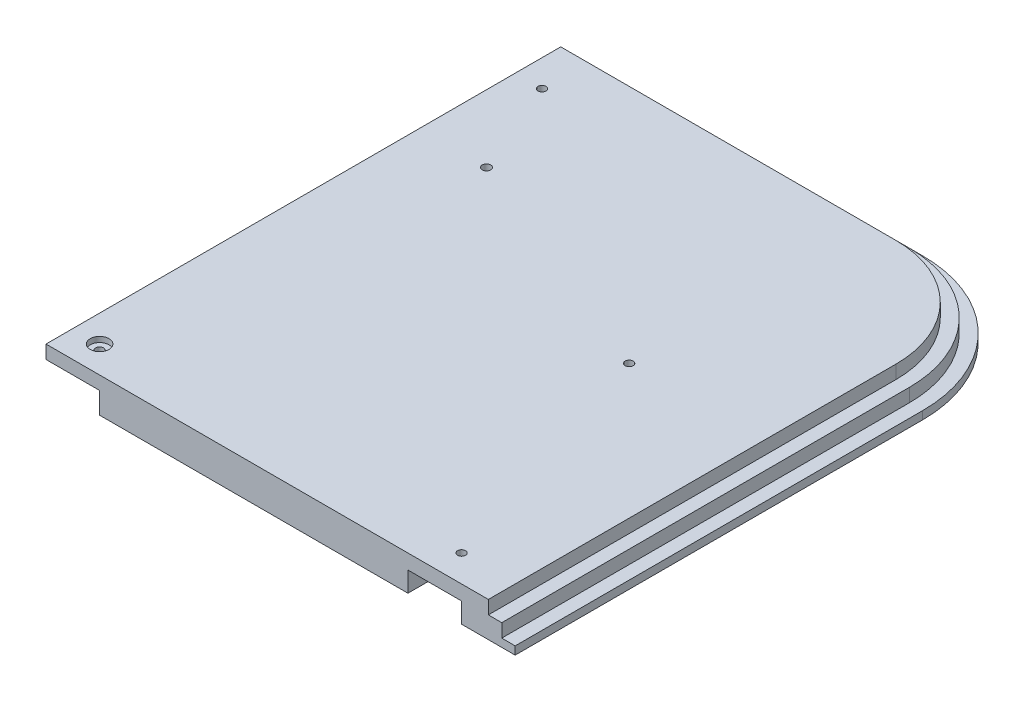
SolidWorks part; units mm, degrees
material "PETG"
ref_plane "Alzado" through (0, 0, 0) normal (0, 0, 1) x (1, 0, 0)
ref_plane "Planta" through (0, 0, 0) normal (0, 1, 0) x (1, 0, 0)
ref_plane "Vista lateral" through (0, 0, 0) normal (1, 0, 0) x (0, 0, -1)
sketch "Croquis1" plane through (0, 0, 0) normal (0, 1, 0) x (1, 0, 0)
  line L1 (125, 225) -> (-125, 225)
  line L2 (175, 175) -> (175, -175)
  line L3 (125, -225) -> (-125, -225)
  line L4 (-175, 175) -> (-175, -175)
  line L5 (175, 225) -> (-175, -225) construction
  line L6 (175, -225) -> (-175, 225) construction
  arc A0 (-125, -225) -> (-175, -175) centre (-125, -175) cw
  arc A1 (175, -175) -> (125, -225) centre (125, -175) cw
  arc A2 (125, 225) -> (175, 175) centre (125, 175) cw
  arc A3 (-125, 225) -> (-175, 175) centre (-125, 175) ccw
  point P0 (0, 0)
  dimension "D3" = 50
  dimension "D1" = 450
  dimension "D2" = 350
extrude "Saliente-Extruir1" add sketch "Croquis1" along normal blind 3
sketch "Croquis2" plane through (0, 3, 0) normal (0, 1, 0) x (1, 0, 0)
  line L8 (-125, -220) -> (125, -220)
  line L9 (170, -175) -> (170, 175)
  line L10 (125, 220) -> (-125, 220)
  line L11 (-170, 175) -> (-170, -175)
  line L12 (-125, -220) -> (125, -220)
  line L13 (170, -175) -> (170, 175)
  line L14 (125, 220) -> (-125, 220)
  line L15 (-170, 175) -> (-170, -175)
  arc A8 (-170, -175) -> (-125, -220) centre (-125, -175) ccw
  arc A9 (125, -220) -> (170, -175) centre (125, -175) ccw
  arc A10 (170, 175) -> (125, 220) centre (125, 175) ccw
  arc A11 (-125, 220) -> (-170, 175) centre (-125, 175) ccw
  arc A12 (-170, -175) -> (-125, -220) centre (-125, -175) ccw
  arc A13 (125, -220) -> (170, -175) centre (125, -175) ccw
  arc A14 (170, 175) -> (125, 220) centre (125, 175) ccw
  arc A15 (-125, 220) -> (-170, 175) centre (-125, 175) ccw
  dimension "D1" = 5
extrude "Saliente-Extruir2" add sketch "Croquis2" along normal blind 5
sketch "Croquis3" plane through (0, 8, 0) normal (0, 1, 0) x (1, 0, 0)
  line L8 (-125, -215) -> (125, -215)
  line L9 (165, -175) -> (165, 175)
  line L10 (125, 215) -> (-125, 215)
  line L11 (-165, 175) -> (-165, -175)
  line L12 (-125, -215) -> (125, -215)
  line L13 (165, -175) -> (165, 175)
  line L14 (125, 215) -> (-125, 215)
  line L15 (-165, 175) -> (-165, -175)
  arc A8 (-165, -175) -> (-125, -215) centre (-125, -175) ccw
  arc A9 (125, -215) -> (165, -175) centre (125, -175) ccw
  arc A10 (165, 175) -> (125, 215) centre (125, 175) ccw
  arc A11 (-125, 215) -> (-165, 175) centre (-125, 175) ccw
  arc A12 (-165, -175) -> (-125, -215) centre (-125, -175) ccw
  arc A13 (125, -215) -> (165, -175) centre (125, -175) ccw
  arc A14 (165, 175) -> (125, 215) centre (125, 175) ccw
  arc A15 (-125, 215) -> (-165, 175) centre (-125, 175) ccw
  dimension "D1" = 5
extrude "Saliente-Extruir3" add sketch "Croquis3" along normal blind 5
sketch "Croquis6" plane through (0, 13, 0) normal (0, 1, 0) x (1, 0, 0)
  line L0 (0, 0) -> (0, -215) construction
  line L1 (-125, -215) -> (125, -215) construction
  circle A0 centre (-87, -130) radius 2.25
  circle A1 centre (-87, -70) radius 2.25
  circle A2 centre (-87, -10) radius 2.25
  circle A3 centre (87, -130) radius 2.25
  circle A4 centre (87, -70) radius 2.25
  circle A5 centre (87, -10) radius 2.25
  dimension "D1" = 4.5
  dimension "D2" = 4.5
  dimension "D3" = 4.5
  dimension "D4" = 87
  dimension "D5" = 60
  dimension "D6" = 60
  dimension "D7" = 10
extrude "Cortar-Extruir3" cut sketch "Croquis6" against normal blind 5
sketch "Croquis7" plane through (0, 13, 0) normal (0, 1, 0) x (1, 0, 0)
  line L0 (0, -11.4875) -> (0, -220) construction
  line L1 (-125, -220) -> (125, -220) construction
  circle A0 centre (-115, -70) radius 1.5
  circle A1 centre (-115, 125.5) radius 1.5
  circle A2 centre (115, -70) radius 1.5
  circle A3 centre (115, 125.5) radius 1.5
  dimension "D1" = 3
  dimension "D2" = 3
  dimension "D3" = 115
  dimension "D4" = 70
  dimension "D5" = 125.5
  dimension "D6" = 115
extrude "Cortar-Extruir4" cut sketch "Croquis7" against normal through all
sketch "Croquis8" plane through (0, 13, 0) normal (0, 1, 0) x (1, 0, 0)
  line L0 (13.0147, -158) -> (13.0147, -178) construction
  line L4 (16.0147, -158) -> (16.0147, -178)
  line L5 (10.0147, -158) -> (10.0147, -178)
  line L6 (25.0147, -158) -> (25.0147, -178) construction
  line L7 (28.0147, -158) -> (28.0147, -178)
  line L8 (22.0147, -158) -> (22.0147, -178)
  line L9 (25.0147, -106) -> (25.0147, -126) construction
  line L10 (28.0147, -106) -> (28.0147, -126)
  line L11 (22.0147, -106) -> (22.0147, -126)
  line L12 (13.0147, -106) -> (13.0147, -126) construction
  line L15 (16.0147, -106) -> (16.0147, -126)
  line L16 (10.0147, -106) -> (10.0147, -126)
  arc A0 (10.0147, -168) -> (13.0147, -171) centre (13.0147, -168) ccw construction
  arc A1 (25.0147, -171) -> (28.0147, -168) centre (25.0147, -168) ccw construction
  arc A2 (16.0147, -116) -> (13.0147, -113) centre (13.0147, -116) ccw construction
  arc A3 (22.0147, -116) -> (25.0147, -119) centre (25.0147, -116) ccw construction
  arc A6 (16.0147, -158) -> (10.0147, -158) centre (13.0147, -158) ccw
  arc A7 (10.0147, -178) -> (16.0147, -178) centre (13.0147, -178) ccw
  arc A8 (28.0147, -158) -> (22.0147, -158) centre (25.0147, -158) ccw
  arc A9 (22.0147, -178) -> (28.0147, -178) centre (25.0147, -178) ccw
  arc A10 (28.0147, -106) -> (22.0147, -106) centre (25.0147, -106) ccw
  arc A11 (22.0147, -126) -> (28.0147, -126) centre (25.0147, -126) ccw
  arc A14 (16.0147, -106) -> (10.0147, -106) centre (13.0147, -106) ccw
  arc A15 (10.0147, -126) -> (16.0147, -126) centre (13.0147, -126) ccw
  arc A16 (13.0147, -113) -> (10.0147, -116) centre (13.0147, -116) ccw construction
  arc A17 (10.0147, -116) -> (13.0147, -119) centre (13.0147, -116) ccw construction
  arc A18 (13.0147, -119) -> (16.0147, -116) centre (13.0147, -116) ccw construction
  arc A19 (28.0147, -116) -> (25.0147, -113) centre (25.0147, -116) ccw construction
  arc A20 (25.0147, -119) -> (28.0147, -116) centre (25.0147, -116) ccw construction
  arc A21 (25.0147, -113) -> (22.0147, -116) centre (25.0147, -116) ccw construction
  arc A22 (25.0147, -165) -> (22.0147, -168) centre (25.0147, -168) ccw construction
  arc A23 (22.0147, -168) -> (25.0147, -171) centre (25.0147, -168) ccw construction
  arc A24 (28.0147, -168) -> (25.0147, -165) centre (25.0147, -168) ccw construction
  arc A25 (16.0147, -168) -> (13.0147, -165) centre (13.0147, -168) ccw construction
  arc A26 (13.0147, -171) -> (16.0147, -168) centre (13.0147, -168) ccw construction
  arc A27 (13.0147, -165) -> (10.0147, -168) centre (13.0147, -168) ccw construction
  point P10 (13.0147, -168)
  point P16 (25.0147, -168)
  point P23 (25.0147, -116)
  point P32 (13.0147, -116)
  dimension "D1" = 6
  dimension "D2" = 6
  dimension "D3" = 6
  dimension "D4" = 6
  dimension "D5" = 12
  dimension "D6" = 52
  dimension "D7" = 116
  dimension "D8" = 13.0147
  dimension "D9" = 20
  dimension "D10" = 20
  dimension "D11" = 20
  dimension "D12" = 20
extrude "Cortar-Extruir5" cut sketch "Croquis8" against normal blind 8
sketch "Croquis9" plane through (0, 13, 0) normal (0, 1, 0) x (1, 0, 0)
  circle A0 centre (13.0147, -168) radius 1.5
  circle A1 centre (25.0147, -168) radius 1.5
  circle A2 centre (13.0147, -116) radius 1.5
  circle A3 centre (25.0147, -116) radius 1.5
  circle A4 centre (-87, -70) radius 2.25 construction
  circle A5 centre (-87, -130) radius 1.5
  circle A6 centre (-87, -70) radius 1.5
  circle A7 centre (-87, -10) radius 1.5
  circle A8 centre (87, -10) radius 1.5
  circle A9 centre (87, -70) radius 1.5
  circle A10 centre (87, -130) radius 1.5
  dimension "D1" = 3
  dimension "D2" = 3
  dimension "D3" = 3
  dimension "D4" = 3
  dimension "D5" = 100.0147
  dimension "D6" = 112.0147
  dimension "D7" = 46
  dimension "D8" = 98
extrude "Cortar-Extruir6" cut sketch "Croquis9" against normal through all
sketch "Croquis10" plane through (0, 13, 0) normal (0, 1, 0) x (1, 0, 0)
  line L1 (50, -120) -> (75, -120)
  line L2 (50, -120) -> (50, -170)
  line L3 (50, -170) -> (75, -170)
  line L4 (75, -120) -> (75, -170)
  dimension "D1" = 50
  dimension "D2" = 25
  dimension "D3" = 120
  dimension "D4" = 50
extrude "Cortar-Extruir7" cut sketch "Croquis10" against normal blind 5
chamfer "Chaflán1" distance 5 angle 45 4 edges at (62.5, 13, 120) (50, 13, 145) (62.5, 13, 170) (75, 13, 145)
sketch "Croquis13" plane through (0, 13, 0) normal (0, 1, 0) x (1, 0, 0)
  circle A0 centre (-60, -50) radius 2.25
  circle A1 centre (-20, -50) radius 2.25
  circle A2 centre (-20, -90) radius 2.25
  circle A3 centre (-60, -90) radius 2.25
  circle A4 centre (-20, -50) radius 3.5
  circle A5 centre (-60, -50) radius 3.5
  circle A6 centre (-60, -90) radius 3.5
  circle A7 centre (-20, -90) radius 3.5
  dimension "D1" = 4.5
  dimension "D2" = 40
  dimension "D6" = 7
  dimension "D3" = 40
  dimension "D4" = 20
  dimension "D5" = 50
extrude "Saliente-Extruir4" add sketch "Croquis13" along normal blind 25
sketch "Croquis14" plane through (0, 13, 0) normal (0, 1, 0) x (1, 0, 0)
  circle A0 centre (3.15, -40) radius 1.25
  circle A1 centre (67.55, -40) radius 1.25
  circle A3 centre (67.55, -40) radius 3
  circle A4 centre (3.15, -40) radius 3
  circle A5 centre (3, -91.9) radius 3
  circle A6 centre (3, -91.9) radius 1.25
  circle A7 centre (67.4, -91.9) radius 3
  circle A8 centre (67.4, -91.9) radius 1.25
  circle A9 centre (-10, -102.9) radius 1.5
  circle A10 centre (-10, -102.9) radius 3
  circle A11 centre (-10, -118.1085) radius 3
  circle A12 centre (-10, -118.1085) radius 1.5
  dimension "D1" = 2.5
  dimension "D2" = 6
  dimension "D7" = 3
  dimension "D8" = 6
  dimension "D9" = 6
  dimension "D10" = 3
  dimension "D3" = 51.9
  dimension "D4" = 64.4
  dimension "D5" = 40
  dimension "D6" = 3
  dimension "D11" = 11
  dimension "D12" = 13
  dimension "D13" = 15.2085
  dimension "D14" = 64.4
  dimension "D15" = 0.15
extrude "Saliente-Extruir5" add sketch "Croquis14" along normal blind 10
sketch "Croquis12" plane through (0, 13, 0) normal (0, 1, 0) x (1, 0, 0)
  line L0 (-25.1, 12) -> (-25.1, 13.6) construction
  line L1 (-25.1, 12) -> (-23.5, 12) construction
  line L2 (25.1, 12) -> (23.5, 12) construction
  line L3 (25.1, 12) -> (25.1, 13.6) construction
  line L4 (25.1, 162.2) -> (25.1, 160.6) construction
  line L5 (25.1, 162.2) -> (23.5, 162.2) construction
  line L6 (-25.1, 162.2) -> (-23.5, 162.2) construction
  line L7 (-25.1, 162.2) -> (-25.1, 160.6) construction
  circle A0 centre (-25.1, 162.2) radius 1.6
  circle A1 centre (25.1, 162.2) radius 1.6
  circle A2 centre (-25.1, 12) radius 1.6
  circle A3 centre (25.1, 12) radius 1.6
  dimension "D4" = 3.2
  dimension "D1" = 12
  dimension "D2" = 47
  dimension "D3" = 23.5
  dimension "D5" = 147
  dimension "D6" = 147
extrude "Cortar-Extruir9" cut sketch "Croquis12" against normal through all
sketch "Croquis11" plane through (0, 0, 0) normal (0, -1, 0) x (1, 0, 0)
  line L0 (13.0147, 168) -> (25.0147, 168) construction
  line L1 (13.0147, 188) -> (25.0147, 188)
  line L2 (13.0147, 148) -> (25.0147, 148)
  line L3 (13.0147, 116) -> (25.0147, 116) construction
  line L4 (13.0147, 136) -> (25.0147, 136)
  line L5 (13.0147, 96) -> (25.0147, 96)
  circle A4 centre (87, 130) radius 6
  circle A5 centre (87, 70) radius 6
  circle A6 centre (87, 10) radius 6
  circle A7 centre (-87, 10) radius 6
  circle A8 centre (-87, 70) radius 6
  circle A9 centre (-87, 130) radius 6
  circle A10 centre (-115, 70) radius 6
  circle A11 centre (115, 70) radius 6
  circle A12 centre (115, -125.5) radius 6
  circle A15 centre (-115, -125.5) radius 6
  arc A16 (13.0147, 188) -> (13.0147, 148) centre (13.0147, 168) ccw
  arc A17 (25.0147, 148) -> (25.0147, 188) centre (25.0147, 168) ccw
  circle A18 centre (-25.1, -162.2) radius 6
  arc A19 (13.0147, 136) -> (13.0147, 96) centre (13.0147, 116) ccw
  arc A20 (25.0147, 96) -> (25.0147, 136) centre (25.0147, 116) ccw
  circle A21 centre (25.1, -162.2) radius 6
  circle A22 centre (-25.1, -12) radius 6
  circle A23 centre (25.1, -12) radius 6
  point P3 (19.0147, 168)
  point P10 (19.0147, 116)
  dimension "D1" = 12
  dimension "D2" = 20
  dimension "D3" = 20
extrude "Cortar-Extruir8" cut sketch "Croquis11" against normal blind 5
sketch "Croquis16" plane through (0, 0, 0) normal (1, 0, 0) x (0, 0, -1)
  line L0 (-175, 0) -> (175, 0) construction
  line L5 (-175, 8) -> (175, 8) construction
  line L6 (2, 8) -> (42, 8)
  line L7 (2, 8) -> (2, 0)
  line L8 (2, 0) -> (42, 0)
  line L9 (42, 8) -> (42, 0)
  dimension "D1" = 40
  dimension "D2" = 2
extrude "Cortar-Extruir10" cut sketch "Croquis16" against normal mid plane 40
sketch "Croquis17" plane through (0, 13, 0) normal (0, 1, 0) x (1, 0, 0)
  line L0 (-175, 23) -> (0, 23) construction
  line L2 (0, 23) -> (0, -225) construction
  line L3 (-125, -225) -> (125, -225) construction
  line L4 (-175, 175) -> (-175, -175) construction
  line L5 (-175, 23) -> (-175, 225)
  line L6 (-175, 225) -> (0, 225)
  line L7 (175, 225) -> (175, 23) construction
  line L8 (175, -225) -> (0, -225)
  line L9 (125, 225) -> (-125, 225) construction
  line L10 (175, -175) -> (175, 175) construction
  line L11 (0, 23) -> (175, 23)
  line L12 (-175, 23) -> (-175, -225)
  line L13 (-175, -225) -> (0, -225)
  line L14 (175, 23) -> (175, -225)
  line L15 (0, 23) -> (0, 225)
  line L16 (0, 225) -> (175, 225) construction
  dimension "D1" = 248
extrude "Cortar-Extruir11" cut sketch "Croquis17" against normal mid plane 60
sketch "Croquis19" plane through (0, 13, 0) normal (0, 1, 0) x (1, 0, 0)
  line L0 (175, 23) -> (175, 175) construction
  line L1 (165, 23) -> (0, 23) construction
  line L2 (0, 23) -> (0, 215) construction
  line L3 (125, 225) -> (0, 225) construction
  circle A0 centre (10, 33) radius 1.5
  circle A1 centre (10, 198) radius 1.5
  circle A2 centre (145, 33) radius 1.5
  dimension "D1" = 3
  dimension "D2" = 3
  dimension "D3" = 3
  dimension "D4" = 30
  dimension "D5" = 10
  dimension "D6" = 10
  dimension "D7" = 27
  dimension "D8" = 10
extrude "Cortar-Extruir12" cut sketch "Croquis19" against normal blind 70
sketch "Croquis20" plane through (0, 0, 0) normal (-1, 0, 0) x (0, 0, 1)
  line L0 (-225, 0) -> (-225, 3) construction
  line L6 (-208, 7.5) -> (-188, 7.5)
  line L7 (-208, 7.5) -> (-208, 0)
  line L8 (-208, 0) -> (-188, 0)
  line L9 (-188, 7.5) -> (-188, 0)
  line L11 (-225, 0) -> (-42, 0) construction
  dimension "D1" = 17
  dimension "D2" = 20
  dimension "D3" = 7.5
extrude "Cortar-Extruir13" cut sketch "Croquis20" against normal blind 20
sketch "Croquis21" plane through (0, 0, -23) normal (0, 0, 1) x (1, 0, 0)
  line L0 (175, 0) -> (20, 0) construction
  line L1 (135, 7.5) -> (155, 7.5)
  line L2 (135, 7.5) -> (135, 0)
  line L3 (135, 0) -> (155, 0)
  line L4 (155, 7.5) -> (155, 0)
  line L5 (175, 0) -> (175, 3) construction
  dimension "D1" = 7.5
  dimension "D2" = 20
  dimension "D3" = 20
extrude "Cortar-Extruir14" cut sketch "Croquis21" against normal blind 20
sketch "Croquis22" plane through (0, 0, 0) normal (0, -1, 0) x (1, 0, 0)
  line L5 (27, -208) -> (27, -181)
  line L6 (27, -181) -> (0, -181)
  line L7 (27, -215) -> (27, -181)
  line L8 (27, -181) -> (7, -181)
  line L28 (128, -50) -> (128, -30)
  line L29 (128, -30) -> (27, -30)
  line L30 (27, -30) -> (27, -49)
  line L31 (27, -49) -> (7, -49)
  line L32 (7, -49) -> (7, -181)
  line L33 (7, -181) -> (27, -181)
  line L34 (27, -181) -> (27, -215)
  line L35 (27, -215) -> (7, -215)
  line L36 (7, -215) -> (7, -218)
  line L37 (7, -218) -> (125, -218)
  line L38 (168, -175) -> (168, -30)
  line L39 (168, -30) -> (162, -30)
  line L40 (162, -30) -> (162, -50)
  line L41 (162, -50) -> (128, -50)
  line L42 (128, -50) -> (128, -30)
  line L43 (128, -30) -> (27, -30)
  line L44 (27, -30) -> (27, -49)
  line L45 (27, -49) -> (7, -49)
  line L46 (7, -49) -> (7, -181)
  line L49 (27, -215) -> (7, -215)
  line L50 (7, -215) -> (7, -218)
  line L51 (7, -218) -> (125, -218)
  line L52 (168, -175) -> (168, -30)
  line L53 (168, -30) -> (162, -30)
  line L54 (162, -30) -> (162, -50)
  line L55 (162, -50) -> (128, -50)
  arc A2 (125, -218) -> (168, -175) centre (125, -175) ccw
  arc A3 (125, -218) -> (168, -175) centre (125, -175) ccw
  circle A5 centre (115, -125.5) radius 16
  circle A6 centre (115, -125.5) radius 16
  circle A8 centre (25.1, -162.2) radius 16
  circle A9 centre (25.1, -162.2) radius 16
  dimension "D1" = 7
  dimension "D2" = 10
  dimension "D3" = 10
  dimension "D4" = 7
extrude "Cortar-Extruir15" cut sketch "Croquis22" against normal blind 6
sketch "Croquis23" plane through (0, 13, 0) normal (0, 1, 0) x (1, 0, 0)
  circle A3 centre (10, 33) radius 3.5
  circle A4 centre (10, 33) radius 3.5
  dimension "D1" = 2
extrude "Cortar-Extruir16" cut sketch "Croquis23" against normal blind 2
